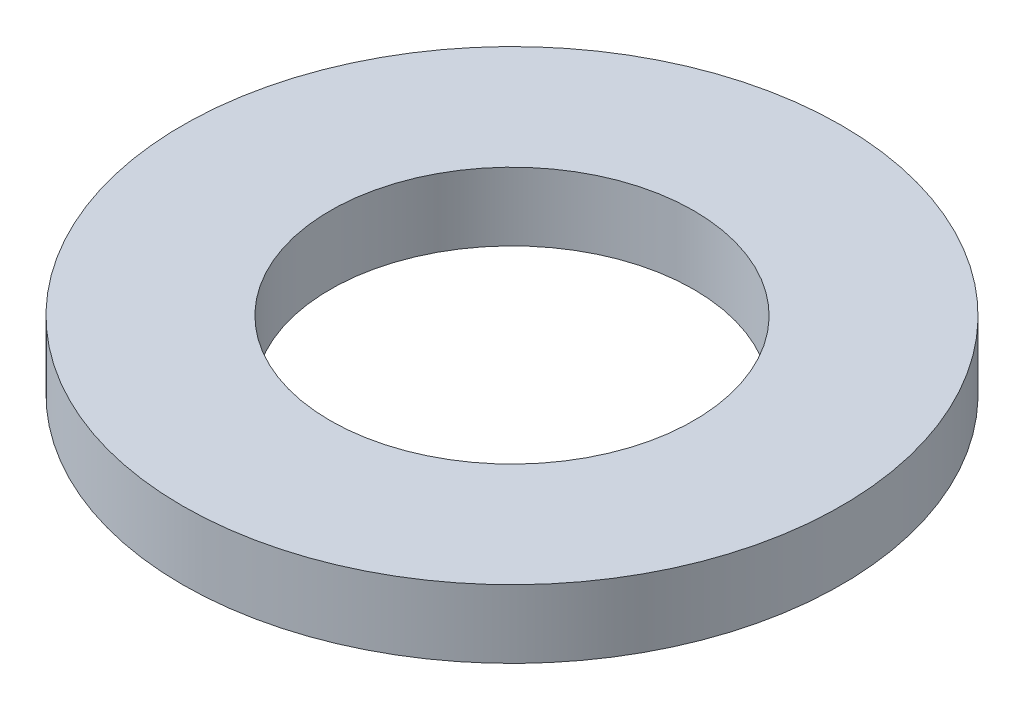
SolidWorks part; units mm, degrees
ref_plane "Front Plane" through (0, 0, 0) normal (0, 0, 1) x (1, 0, 0)
ref_plane "Top Plane" through (0, 0, 0) normal (0, 1, 0) x (1, 0, 0)
ref_plane "Right Plane" through (0, 0, 0) normal (1, 0, 0) x (0, 0, -1)
sketch "Sketch1" plane through (0, 0, 0) normal (0, 1, 0) x (1, 0, 0)
  circle A0 centre (0, 0) radius 72.5
  dimension "FLANGE_OD" = 145
extrude "Boss-Extrude1" add sketch "Sketch1" along normal blind 15
sketch "Sketch2" plane through (0, 0, 0) normal (0, 1, 0) x (1, 0, 0)
  circle A0 centre (0, 0) radius 40
  dimension "BORE_D" = 80
extrude "Cut-Extrude1" cut sketch "Sketch2" along normal through all
sketch "Sketch3" plane through (0, 15, 0) normal (0, 1, 0) x (1, 0, 0)
  circle A0 centre (0, 0) radius 21.9173 construction
  circle A1 centre (-21.9173, 0) radius 1.7172
  dimension "BOLT_D" = 3.4345
  dimension "BOLT_PCD" = 43.8347
extrude "Cut-Extrude2" cut sketch "Sketch3" against normal blind 12.835 rebuild error yes
pattern_circular "CirPattern1" count 8 over 360 rebuild error yes
